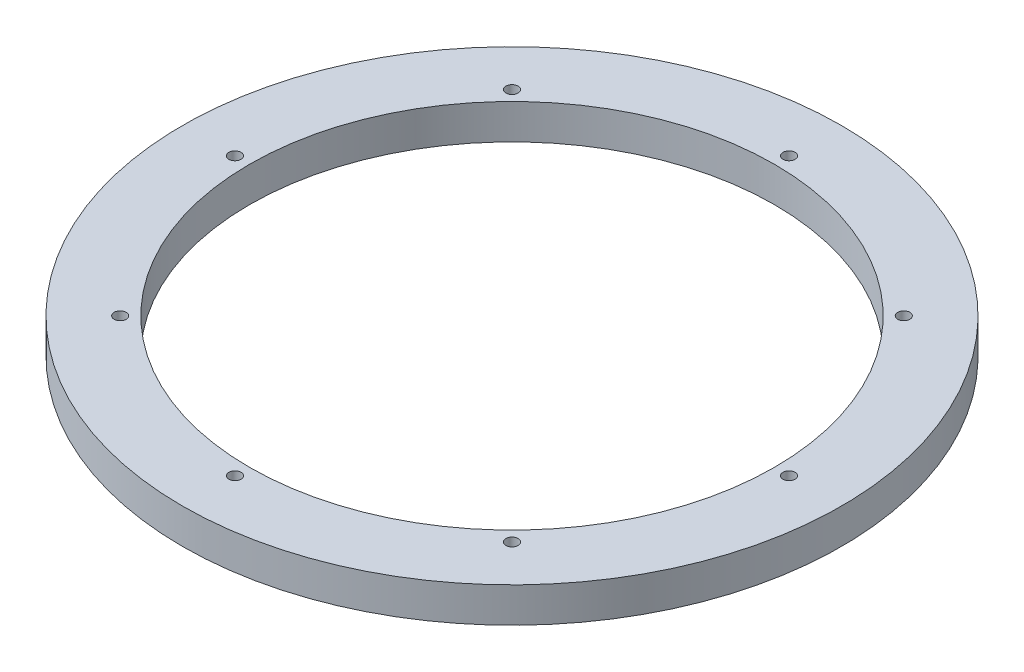
SolidWorks part; units mm, degrees
material "6061 Alloy"
ref_plane "Front Plane" through (0, 0, 0) normal (0, 0, 1) x (1, 0, 0)
ref_plane "Top Plane" through (0, 0, 0) normal (0, 1, 0) x (1, 0, 0)
ref_plane "Right Plane" through (0, 0, 0) normal (1, 0, 0) x (0, 0, -1)
sketch "Sketch1" plane through (0, 0, 0) normal (0, 1, 0) x (1, 0, 0)
  circle A0 centre (0, 0) radius 57.15
  circle A1 centre (0, 0) radius 71.755
  circle A2 centre (0, 0) radius 68.58
  circle A3 centre (0, -60.325) radius 1.3208
  circle A4 centre (-42.6562, -42.6562) radius 1.3208
  circle A5 centre (-60.325, 0) radius 1.3208
  circle A6 centre (-42.6562, 42.6562) radius 1.3208
  circle A7 centre (0, 60.325) radius 1.3208
  circle A8 centre (42.6562, 42.6562) radius 1.3208
  circle A9 centre (60.325, 0) radius 1.3208
  circle A10 centre (42.6562, -42.6562) radius 1.3208
  point P21 (0, 0)
  dimension "D1" = 114.3
  dimension "D4" = 2.6416
  dimension "D5" = 60.325
  dimension "D2" = 14.605
  dimension "D3" = 11.43
  dimension "D6" = 8
extrude "Boss-Extrude1" add sketch "Sketch1" along normal blind 7.62 contours A2 A0 | A1 A2 region at (-69.7255, 0, 0) region at (-66.6403, 0, 0)
sketch "Sketch2" plane through (0, 0, 0) normal (1, 0, 0) x (0, 0, -1)
  line L0 (-71.755, 0) -> (71.755, 0) construction
  line L1 (71.755, 7.62) -> (-71.755, 7.62) construction
  line L2 (-71.755, 0) -> (71.755, 0)
  line L3 (71.755, 7.62) -> (-71.755, 7.62)
  line L4 (89.5975, 6.858) -> (99.9841, 6.858) construction
  line L5 (95.9885, 5.08) -> (99.6739, 5.08) construction
  line L6 (0, 0) -> (0, 18.217) construction
  circle A0 centre (68.58, 8.4455) radius 1.5875 construction
  circle A1 centre (68.58, 8.509) radius 1.651
  circle A2 centre (68.58, 1.651) radius 1.651
  dimension "D3" = 3.175
  dimension "D4" = 3.302
  dimension "D1" = 68.58
  dimension "D2" = 0.762
  dimension "D5" = 2.54
equation "\"Middle Coupler Inner Daimeter\"= 4.5in"
equation "\"Middle Coupler  Wall Thickness\" = 0.25in"
equation "\"Middle Coupler Bottom Thickness\"= 0.2in"
equation "\"Bearing Rail Offset\"= 0.45in"
equation "\"3-56 UNF Tap\"= 0.089in"
equation "\"3-56 UNF Clearance\"= 0.104in"
equation "\"D5@Sketch1\"=(\"Middle Coupler Inner Daimeter\"*2+0.5)/4in"
equation "\"Ball Bearing Distance\"= 0.03in"
equation "\"D1@Sketch2\"=\"Middle Coupler Inner Daimeter\"/2+\"Bearing Rail Offset\""
equation "\"D3@Sketch1\"=\"Bearing Rail Offset\""
equation "\"D4@Sketch1\"=\"3-56 UNF Clearance\""
equation "\"D1@Sketch1\"=\"Middle Coupler Inner Daimeter\""
equation "\"D2@Sketch2\"=\"Ball Bearing Distance\""
equation "\"D4@Sketch2\"=\"D3@Sketch2\"+0.005"
equation "\"D5@Sketch2\"=\"Middle Coupler Bottom Thickness\"/2"
equation "\"TCA Outer Diameter\" = 6.625in"
equation "\"Interstage Aeroframe Wall Thickness\" = 0.072in"
equation "\"Compression Spring OD\"= 0.42in"
equation "\"10-24 Tap\"= 0.157in"
equation "\"10-24 Clearance\"= 0.196in"
equation "\"Lower Stage Fuselage Wall Thickness\" = 0.25in"
equation "\"6-32 Tap\" = 0.107in"
equation "\"1/4-20 Tap\" = 0.201in"
